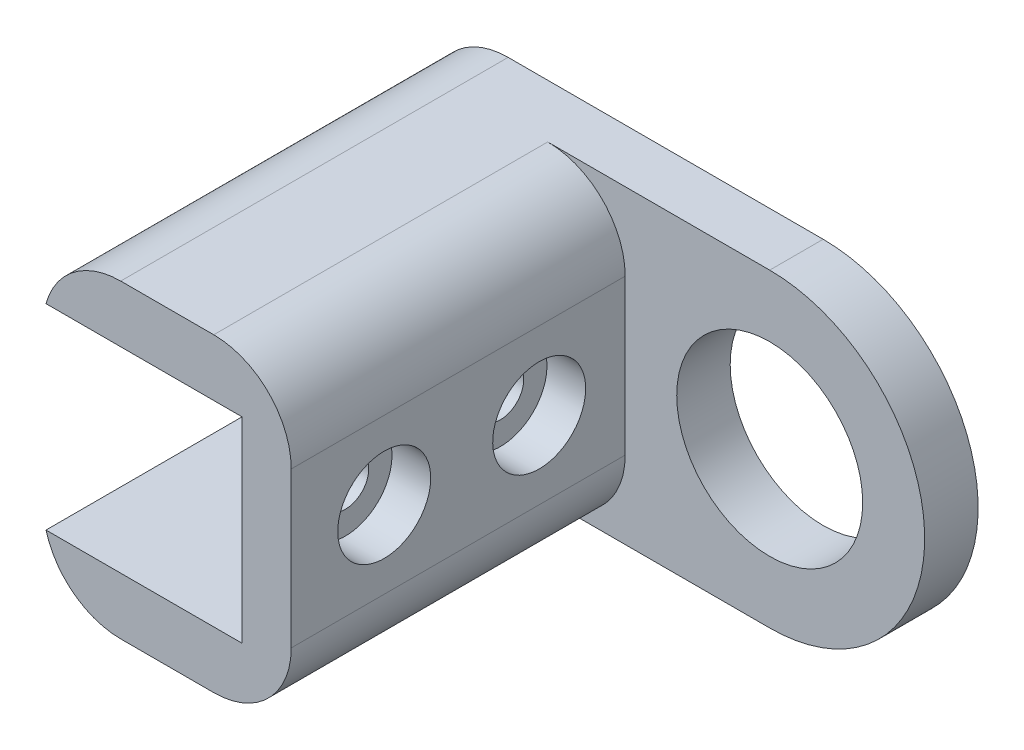
SolidWorks part; units mm, degrees
ref_plane "Front Plane" through (0, 0, 0) normal (0, 0, 1) x (1, 0, 0)
ref_plane "Top Plane" through (0, 0, 0) normal (0, 1, 0) x (1, 0, 0)
ref_plane "Right Plane" through (0, 0, 0) normal (1, 0, 0) x (0, 0, -1)
sketch "Sketch1" plane through (0, 0, 0) normal (0, 0, 1) x (1, 0, 0)
  line L0 (0, 10) -> (-12.5, 10)
  line L1 (-12.5, 10) -> (-12.5, -10)
  line L2 (-12.5, -10) -> (0, -10)
  arc A0 (0, -10) -> (0, 10) centre (0, 0) ccw
  circle A1 centre (0, 0) radius 6
  dimension "D1" = 12
  dimension "D2" = 20
  dimension "D3" = 12.5
extrude "Boss-Extrude1" add sketch "Sketch1" along normal blind 3.45
sketch "Sketch2" plane through (0, 0, 3.45) normal (0, 0, 1) x (1, 0, 0)
  line L0 (-12.5, -10) -> (0, -10) construction
  line L1 (-12.5, 10) -> (-9.325, 10)
  line L2 (-12.5, 10) -> (-12.5, -10)
  line L3 (-12.5, -10) -> (-9.325, -10)
  line L4 (-9.325, 10) -> (-9.325, -10)
  dimension "D1" = 3.175
extrude "Boss-Extrude2" add sketch "Sketch2" along normal offset from surface (21.55 mm away) 25 up to face at (-3.75, 0, 0)
sketch "Sketch3" plane through (-12.5, 0, 0) normal (-1, 0, 0) x (0, 0, 1)
  line L0 (25, 0) -> (0, 0) construction
  line L1 (25, 10) -> (25, -10) construction
  line L2 (0, 10) -> (0, -10) construction
  line L4 (25, 10) -> (0, 10)
  line L5 (25, 10) -> (25, 6.325)
  line L6 (25, 6.325) -> (0, 6.325)
  line L7 (0, 10) -> (0, 6.325)
  line L8 (0, -6.325) -> (25, -6.325)
  line L9 (0, -6.325) -> (0, -10)
  line L10 (0, -10) -> (25, -10)
  line L11 (25, -6.325) -> (25, -10)
  dimension "D1" = 12.65
extrude "Boss-Extrude3" add sketch "Sketch3" along normal blind 12.65
fillet "Fillet1" radius 5 2 edges
sketch "Sketch5" plane through (-9.325, 0, 0) normal (1, 0, 0) x (0, 0, -1)
  line L0 (-25, 0) -> (-3.45, 0) construction
  line L1 (-25, -5) -> (-25, 5) construction
  line L2 (-3.45, -5) -> (-3.45, 5) construction
  circle A0 centre (-19, 0) radius 1.5
  circle A1 centre (-9, 0) radius 1.5
  dimension "D1" = 3
  dimension "D2" = 10
  dimension "D3" = 6
extrude "Cut-Extrude1" cut sketch "Sketch5" against normal blind 12.65
sketch "Sketch6" plane through (-9.325, 0, 0) normal (1, 0, 0) x (0, 0, -1)
  circle A0 centre (-19, 0) radius 3
  circle A1 centre (-9, 0) radius 3
  dimension "D1" = 6
extrude "Cut-Extrude2" cut sketch "Sketch6" against normal blind 2.5
fillet "Fillet2" radius 5 2 edges at (-25.15, 10, 12.5) (-25.15, -10, 12.5)
sketch "Sketch7" plane through (0, 0, 0) normal (0, 0, -1) x (-1, 0, 0)
  line L0 (-10, 0) -> (25.15, 0) construction
  line L1 (25.15, 0) -> (25.15, 6.325) construction
  arc A0 (0, 10) -> (0, -10) centre (0, 0) ccw construction
sketch "Sketch8" plane through (-9.325, 0, 0) normal (1, 0, 0) x (0, 0, -1)
  line L0 (0, -4.6032) -> (0, 10) construction
  line L1 (0, 10) -> (-8.6678, 10) construction
  line L2 (-25, 10) -> (-3.45, 10) construction
  line L3 (0, 6.325) -> (0, -6.325) construction
